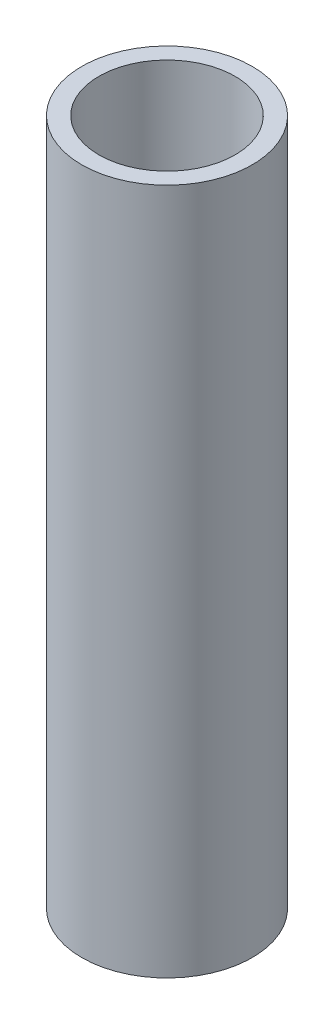
SolidWorks part; units mm, degrees
ref_plane "Front Plane" through (0, 0, 0) normal (0, 0, 1) x (1, 0, 0)
ref_plane "Top Plane" through (0, 0, 0) normal (0, 1, 0) x (1, 0, 0)
ref_plane "Right Plane" through (0, 0, 0) normal (1, 0, 0) x (0, 0, -1)
sketch "Sketch1" plane through (0, 0, 0) normal (0, 1, 0) x (1, 0, 0)
  circle A0 centre (0, 0) radius 12.4187
  circle A1 centre (0, 0) radius 9.9187
  dimension "D1" = 24.8374
  dimension "D2" = 19.8374
extrude "Boss-Extrude1" add sketch "Sketch1" against normal blind 100 contours A0
extrude "Cut-Extrude1" cut sketch "Sketch1<3>" against normal blind 30 contours A1
sketch "Sketch1<3>" plane through (0, 0, 0) normal (0, 1, 0) x (1, 0, 0) same geometry as "Sketch1"
ref_axis "Axis1" through (0, -100, 0) along (0, 1, 0)
equation "\"D1@Sketch1\"=\"D2@Sketch1\"+0.5"
